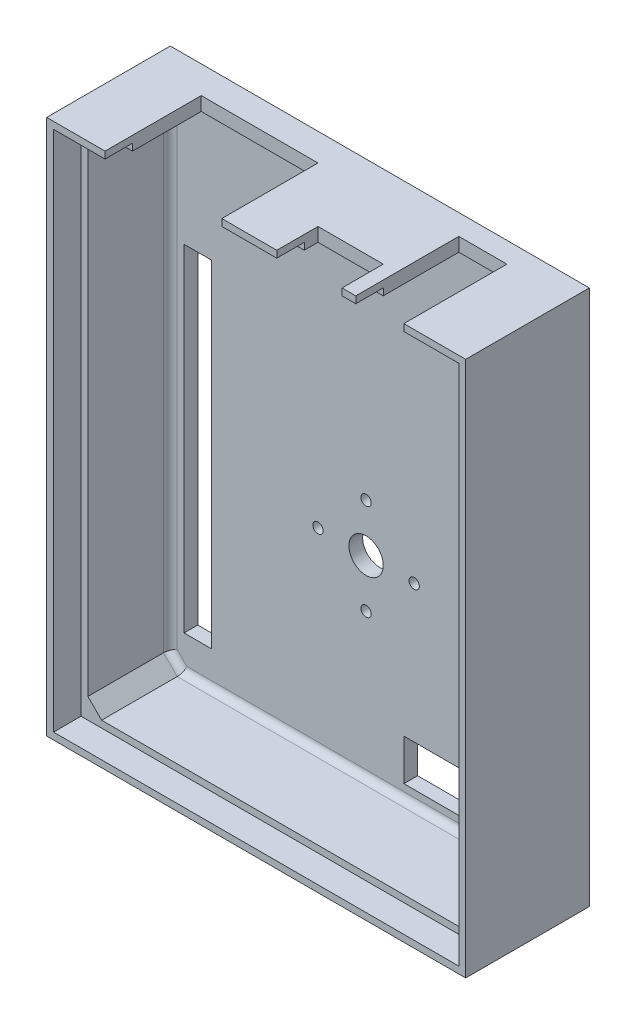
SolidWorks part; units mm, degrees
ref_plane "Plan de face" through (0, 0, 0) normal (0, 0, 1) x (1, 0, 0)
ref_plane "Plan de dessus" through (0, 0, 0) normal (0, 1, 0) x (1, 0, 0)
ref_plane "Plan de droite" through (0, 0, 0) normal (1, 0, 0) x (0, 0, -1)
sketch "Esquisse1" plane through (0, 0, 0) normal (0, 0, 1) x (1, 0, 0)
  line L1 (-30.5, 39) -> (30.5, 39)
  line L2 (-30.5, 39) -> (-30.5, -39)
  line L3 (-30.5, -39) -> (30.5, -39)
  line L4 (30.5, 39) -> (30.5, -39)
  point P4 (0, 39)
  point P6 (-30.5, 0)
  dimension "D1" = 61
  dimension "D2" = 78
extrude "Boss.-Extru.1" add sketch "Esquisse1" along normal blind 2
sketch "Esquisse2" plane through (0, 0, 2) normal (0, 0, 1) x (1, 0, 0)
  line L0 (-30.5, 39) -> (30.5, 39)
  line L1 (30.5, 39) -> (30.5, -39)
  line L2 (30.5, -39) -> (-30.5, -39)
  line L3 (-30.5, -39) -> (-30.5, 39)
  line L5 (-28.5, 37) -> (28.5, 37)
  line L6 (-28.5, 37) -> (-28.5, -37)
  line L7 (-28.5, -37) -> (28.5, -37)
  line L8 (28.5, 37) -> (28.5, -37)
  dimension "D1" = 2
  dimension "D2" = 2
  dimension "D3" = 2
  dimension "D4" = 2
extrude "Boss.-Extru.2" add sketch "Esquisse2" along normal blind 12
sketch "Esquisse3" plane through (0, 0, 14) normal (0, 0, 1) x (1, 0, 0)
  line L1 (-30.5, 39) -> (30.5, 39)
  line L2 (-30.5, 39) -> (-30.5, -39)
  line L3 (-30.5, -39) -> (30.5, -39)
  line L4 (30.5, 39) -> (30.5, -39)
  line L5 (29.5, -38) -> (-29.5, -38)
  line L6 (29.5, -38) -> (29.5, 38)
  line L7 (29.5, 38) -> (-29.5, 38)
  line L8 (-29.5, -38) -> (-29.5, 38)
  dimension "D1" = 1
  dimension "D2" = 1
  dimension "D3" = 1
  dimension "D4" = 1
extrude "Boss.-Extru.3" add sketch "Esquisse3" along normal blind 4
sketch "Esquisse7" plane through (0, 39, 0) normal (0, 1, 0) x (1, 0, 0)
  line L1 (-30.5, -18) -> (-30.5, 0) construction
  line L2 (-22, -4) -> (-5, -4)
  line L3 (-22, -4) -> (-22, -24.9849)
  line L4 (-22, -24.9849) -> (-5, -24.9849)
  line L5 (-5, -4) -> (-5, -24.9849)
  line L7 (30.5, -18) -> (-30.5, -18) construction
  line L8 (30.5, -18) -> (30.5, 0) construction
  line L9 (14.5, -3) -> (21.5, -3)
  line L10 (14.5, -3) -> (14.5, -21.0916)
  line L11 (14.5, -21.0916) -> (21.5, -21.0916)
  line L12 (21.5, -3) -> (21.5, -21.0916)
  line L16 (3, -12) -> (12.5, -12)
  line L17 (3, -12) -> (3, -23.0164)
  line L18 (3, -23.0164) -> (12.5, -23.0164)
  line L19 (12.5, -12) -> (12.5, -23.0164)
  dimension "D1" = 17
  dimension "D2" = 8.5
  dimension "D3" = 14
  dimension "D4" = 7
  dimension "D5" = 9
  dimension "D6" = 15
  dimension "D7" = 9.5
  dimension "D8" = 18
  dimension "D9" = 6
extrude "Enlèv. mat.-Extru.2" cut sketch "Esquisse7" against normal blind 3
sketch "Esquisse8" plane through (0, 0, 0) normal (0, 0, -1) x (-1, 0, 0)
  line L0 (30.5, -39) -> (-30.5, -39) construction
  line L1 (-26.5, 7) -> (-22.5, 7)
  line L2 (-26.5, 7) -> (-26.5, -32)
  line L3 (-26.5, -32) -> (-22.5, -32)
  line L4 (-22.5, 7) -> (-22.5, -32)
  line L5 (22.5, 17) -> (26.5, 17)
  line L6 (22.5, 17) -> (22.5, -32)
  line L7 (22.5, -32) -> (26.5, -32)
  line L8 (26.5, 17) -> (26.5, -32)
  line L9 (30.5, 39) -> (30.5, -39) construction
  line L10 (-30.5, -39) -> (-30.5, 39) construction
  line L12 (-16.5, -29) -> (-5.5, -29)
  line L13 (-16.5, -29) -> (-16.5, -35)
  line L14 (-16.5, -35) -> (-5.5, -35)
  line L15 (-5.5, -29) -> (-5.5, -35)
  dimension "D1" = 4
  dimension "D2" = 4
  dimension "D3" = 39
  dimension "D4" = 49
  dimension "D5" = 7
  dimension "D6" = 4
  dimension "D7" = 4
  dimension "D8" = 6
  dimension "D9" = 11
  dimension "D10" = 14
  dimension "D11" = 4
extrude "Enlèv. mat.-Extru.3" cut sketch "Esquisse8" against normal up to next
chamfer "Chanfrein1" distance 2 angle 45 4 edges at (-28.5, 37, 8) (-28.5, -37, 8) (28.5, -37, 8) (28.5, 37, 8)
sketch "Esquisse9" plane through (0, 0, 0) normal (0, 0, -1) x (-1, 0, 0)
  line L1 (30.5, -39) -> (-30.5, -39) construction
  circle A0 centre (0, -9) radius 2.5
  circle A1 centre (-7, -9) radius 0.75
  circle A2 centre (7, -9) radius 0.75
  circle A3 centre (0, -2) radius 0.75
  circle A4 centre (0, -16) radius 0.75
  dimension "D1" = 5
  dimension "D3" = 1.5
  dimension "D2" = 30
  dimension "D4" = 7
  dimension "D5" = 7
  dimension "D6" = 7
  dimension "D7" = 7
extrude "Enlèv. mat.-Extru.4" cut sketch "Esquisse9" against normal up to next
fillet "Congé1" radius 1 8 edges at (-27.5, 36, 2) (0, 37, 2) (27.5, 36, 2) (28.5, 0, 2) (27.5, -36, 2) (0, -37, 2) (-27.5, -36, 2) (-28.5, 0, 2)
